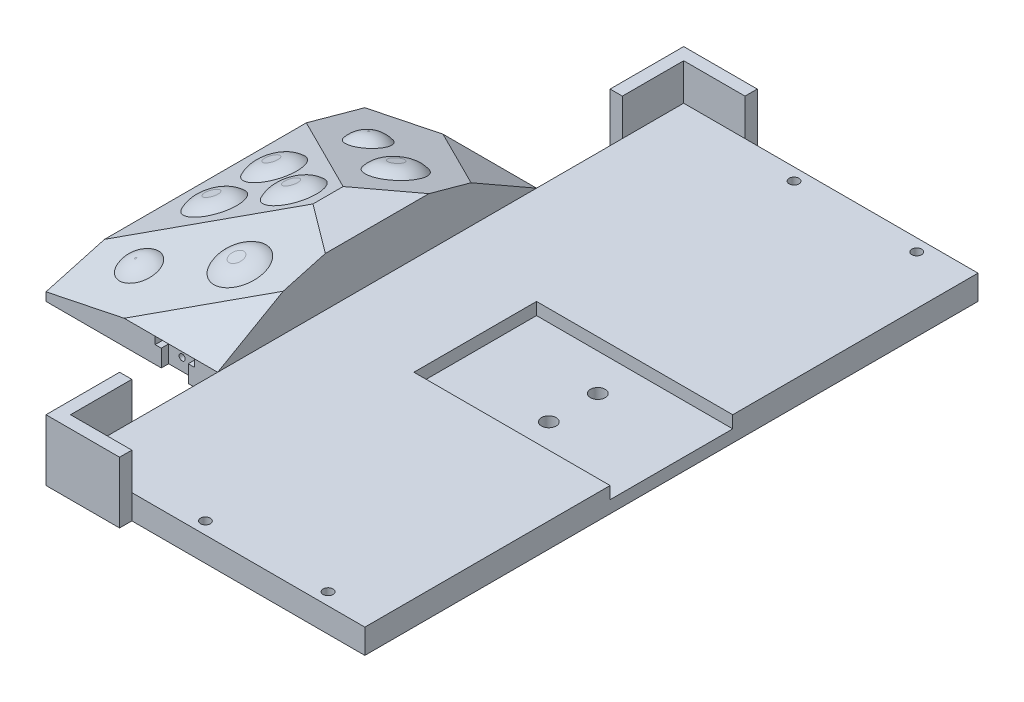
SolidWorks part; units mm, degrees
ref_plane "Ebene vorne" through (0, 0, 0) normal (0, 0, 1) x (1, 0, 0)
ref_plane "Ebene oben" through (0, 0, 0) normal (0, 1, 0) x (1, 0, 0)
ref_plane "Ebene rechts" through (0, 0, 0) normal (1, 0, 0) x (0, 0, -1)
sketch "Skizze1" plane through (0, 0, 0) normal (0, 1, 0) x (1, 0, 0)
  line L5 (-175, -125) -> (175, 125) construction
  line L6 (-175, 125) -> (175, -125) construction
  line L11 (-105, 125) -> (145, 125)
  line L12 (-105, -125) -> (-105, -65)
  line L13 (-105, 125) -> (-105, 65)
  line L14 (-105, -65) -> (-175, -65)
  line L15 (-105, 65) -> (-175, 65)
  line L17 (-105, -125) -> (145, -125)
  line L19 (185, 20) -> (145, 125)
  line L21 (175, 0) -> (175, 20)
  line L22 (175, 20) -> (185, 20)
  line L23 (185, 0) -> (185, 20)
  line L25 (185, 0) -> (185, -20)
  line L26 (185, -20) -> (175, -20)
  line L27 (175, 0) -> (175, -20)
  line L28 (185, -20) -> (145, -125)
  line L29 (-175, 65) -> (-175, -65)
  point P0 (0, 0)
  dimension "D1" = 350
  dimension "D2" = 250
  dimension "D3" = 60
  dimension "D4" = 250
  dimension "D5" = 40
  dimension "D6" = 130
  dimension "D7" = 70
  dimension "D8" = 20
  dimension "D9" = 10
extrude "Aufsatz-Linear austragen1" add sketch "Skizze1" along normal blind 15 contours L15 L29 L14 L12 L17 L28 L26 L27 L21 L22 L19 L11 L13 | L21 L27 L26 L25 L23 L22 region at (10.8182, 0, 0) region at (180, 0, 0)
sketch "Skizze2" plane through (0, 15, 0) normal (0, 1, 0) x (1, 0, 0)
  line L0 (-175, 65) -> (-175, -65) construction
  line L9 (-175, 62) -> (-110, 62)
  line L10 (-175, 62) -> (-175, 42)
  line L11 (-175, 42) -> (-110, 42)
  line L12 (-110, 62) -> (-110, 42)
  line L13 (-105, 65) -> (-175, 65) construction
  line L14 (-175, -42) -> (-110, -42)
  line L15 (-175, -42) -> (-175, -62)
  line L16 (-175, -62) -> (-110, -62)
  line L17 (-110, -42) -> (-110, -62)
  line L18 (-105, -65) -> (-175, -65) construction
  line L19 (-105, 125) -> (145, 125) construction
  line L24 (-125, -62) -> (-120, -62)
  line L25 (-125, -62) -> (-125, -65)
  line L26 (-125, -65) -> (-120, -65)
  line L27 (-120, -62) -> (-120, -65)
  line L28 (-125, -42) -> (-120, -42)
  line L29 (-125, -42) -> (-125, -38)
  line L30 (-125, -38) -> (-120, -38)
  line L31 (-120, -42) -> (-120, -38)
  line L32 (-125, 42) -> (-120, 42)
  line L33 (-125, 42) -> (-125, 38)
  line L34 (-125, 38) -> (-120, 38)
  line L35 (-120, 42) -> (-120, 38)
  line L36 (-125, 65) -> (-120, 65)
  line L37 (-125, 65) -> (-125, 62)
  line L38 (-125, 62) -> (-120, 62)
  line L39 (-120, 65) -> (-120, 62)
  line L40 (-105, -125) -> (145, -125)
  line L41 (-105, -125) -> (-105, 125)
  line L42 (-105, 125) -> (145, 125)
  line L43 (145, -125) -> (145, 125)
  line L46 (145, -125) -> (195, -125)
  line L47 (145, -125) -> (145, 125)
  line L48 (145, 125) -> (195, 125)
  line L49 (195, -125) -> (195, 125)
  line M8 (-105, 65) -> (-175, 65)
  dimension "D1" = 65
  dimension "D2" = 65
  dimension "D3" = 20
  dimension "D4" = 20
  dimension "D5" = 3
  dimension "D6" = 3
  dimension "D7" = 5
  dimension "D8" = 50
  dimension "D9" = 5
  dimension "D10" = 50
  dimension "D11" = 5
  dimension "D12" = 50
  dimension "D13" = 5
  dimension "D14" = 50
  dimension "D15" = 4
  dimension "D16" = 4
  dimension "D17" = 250
  dimension "D18" = 50
extrude "Aufsatz-Linear austragen2" add sketch "Skizze2" against normal blind 37 contours L14 L31 L30 L29 | L35 L11 L33 L34 | L39 L37 L9 M8 | L26 L27 L24 L25 region at (-122.5, 15, -63.5) region at (-122.5, 15, -40) region at (-122.5, 15, 40)
sketch "Skizze3" plane through (0, 15, 0) normal (0, 1, 0) x (1, 0, 0)
  line L0 (-105, 125) -> (145, 125) construction
  line L1 (-105, -125) -> (145, -125)
  line L2 (-105, -125) -> (-105, 125)
  line L3 (-105, 125) -> (145, 125)
  line L4 (145, -125) -> (145, 125)
  line L6 (145, -125) -> (195, -125)
  line L7 (145, -125) -> (145, 125)
  line L8 (145, 125) -> (195, 125)
  line L9 (195, -125) -> (195, 125)
  line M6 (145, -125) -> (185, -20)
  line M7 (185, -20) -> (185, 20)
  line M8 (185, 20) -> (145, 125)
  dimension "D1" = 250
  dimension "D2" = 50
extrude "Aufsatz-Linear austragen3" add sketch "Skizze3" against normal blind 15 contours L6 L9 L8 M8 M7 M6 region at (167.3825, 15, 73.4076)
sketch "Skizze4" plane through (0, 15, 0) normal (0, 1, 0) x (1, 0, 0)
  line L9 (195, -125) -> (200, -125)
  line L10 (195, -125) -> (195, 125)
  line L11 (195, 125) -> (200, 125)
  line L12 (200, -125) -> (200, 125)
  dimension "D3" = 250
  dimension "D4" = 5
extrude "Aufsatz-Linear austragen4" add sketch "Skizze4" against normal blind 15
sketch "Skizze5" plane through (0, 15, 0) normal (0, 1, 0) x (1, 0, 0)
  line L1 (-105, 125) -> (-75, 125)
  line L2 (-105, 125) -> (-105, 120)
  line L3 (-105, 120) -> (-75, 120)
  line L4 (-75, 125) -> (-75, 120)
  line L5 (-105, -125) -> (-75, -125)
  line L6 (-105, -125) -> (-105, -120)
  line L7 (-105, -120) -> (-75, -120)
  line L8 (-75, -125) -> (-75, -120)
  dimension "D1" = 30
  dimension "D2" = 30
  dimension "D3" = 5
  dimension "D4" = 5
extrude "Aufsatz-Linear austragen5" add sketch "Skizze5" against normal blind 30
sketch "Skizze6" plane through (0, 15, 0) normal (0, 1, 0) x (1, 0, 0)
  line L0 (-105, -125) -> (200, -125) construction
  line L1 (-110, -130) -> (-70.4119, -130)
  line L2 (-110, -130) -> (-110, -86.8064)
  line L3 (-110, -86.8064) -> (-70.4119, -86.8064)
  line L4 (-70.4119, -130) -> (-70.4119, -86.8064)
  line L5 (-110, 130) -> (-61.5934, 130)
  line L6 (-110, 130) -> (-110, 88.8696)
  line L7 (-110, 88.8696) -> (-61.5934, 88.8696)
  line L8 (-61.5934, 130) -> (-61.5934, 88.8696)
  line L9 (-105, -125) -> (-105, -65) construction
  line L10 (-105, 125) -> (-105, 65) construction
  line L11 (-105, 125) -> (200, 125) construction
  line L12 (-68.8744, -125) -> (-105, -125)
  line L13 (-105, -125) -> (-105, -86.8064)
  line L14 (-105, 84.0053) -> (-105, 125)
  line L15 (-105, 125) -> (-61.5934, 125)
  line M6 (-105, -65) -> (-105, -125)
  line M7 (-105, -125) -> (200, -125)
  line M9 (200, 125) -> (-105, 125)
  line M10 (-105, 125) -> (-105, 65)
  dimension "D1" = 5
  dimension "D2" = 5
  dimension "D3" = 5
  dimension "D4" = 5
extrude "Aufsatz-Linear austragen6" add sketch "Skizze6" along normal blind 15 separate body contours L8 L5 L6 L7 M10 M9 | L1 L4 L3 L2 M7 M6 region at (-109.4141, 15, 108.4032) region at (-85.7967, 15, -129.3648)
sketch "Skizze7" plane through (0, 0, 0) normal (0, -1, 0) x (1, 0, 0)
  line L7 (-110, -130) -> (-110, -88.8696)
  line L8 (-110, -88.8696) -> (-105, -88.8696)
  line L9 (-105, -130) -> (-105, -88.8696)
  line L10 (-110, 130) -> (-105, 130)
  line L11 (-110, 130) -> (-110, 86.8064)
  line L12 (-110, 86.8064) -> (-105, 86.8064)
  line L13 (-105, 130) -> (-105, 86.8064)
  line L14 (-110, 130) -> (-70.4119, 130)
  line L15 (-110, 130) -> (-110, 125)
  line L16 (-110, 125) -> (-70.4119, 125)
  line L17 (-70.4119, 130) -> (-70.4119, 125)
  line L18 (-110, -130) -> (-61.5934, -130)
  line L19 (-110, -130) -> (-110, -125)
  line L20 (-110, -125) -> (-61.5934, -125)
  line L21 (-61.5934, -130) -> (-61.5934, -125)
  line M7 (-105, 120) -> (-105, 65)
  line M19 (-105, -65) -> (-105, -120)
  line M22 (-75, -125) -> (200, -125)
  line M24 (200, 125) -> (-75, 125)
extrude "Aufsatz-Linear austragen7" add sketch "Skizze7" against normal blind 15 contours L7 L20 L9 L8 M19 | L20 L7 L18 L9 | L18 L21 L20 L9 M22 | L16 L11 L12 L13 M7 | L11 L16 L13 L10 | L17 L14 L13 L16 M24 region at (-107.5, 0, -127.5) region at (-107.5, 0, -106.9348) region at (-83.2967, 0, -127.5) region at (-107.5, 0, 127.5) region at (-87.7059, 0, 127.5) region at (-107.5, 0, 105.9032)
sketch "Skizze8" plane through (0, 15, 0) normal (0, 1, 0) x (1, 0, 0)
  line L0 (-61.5934, 125) -> (200, 125) construction
  line L1 (-105, -125) -> (145, -125)
  line L2 (-105, -125) -> (-105, 125)
  line L3 (-105, 125) -> (145, 125)
  line L4 (145, -125) -> (145, 125)
  line L6 (150, -130) -> (109.2888, -130)
  line L7 (150, -130) -> (150, -94.2536)
  line L8 (150, -94.2536) -> (109.2888, -94.2536)
  line L9 (109.2888, -130) -> (109.2888, -94.2536)
  line L10 (150, 130) -> (118.9946, 130)
  line L11 (150, 130) -> (150, 95.9912)
  line L12 (150, 95.9912) -> (118.9946, 95.9912)
  line L13 (118.9946, 130) -> (118.9946, 95.9912)
  line M9 (-70.4119, -125) -> (200, -125)
  line M11 (200, 125) -> (-61.5934, 125)
  dimension "D1" = 250
  dimension "D2" = 5
  dimension "D3" = 5
  dimension "D4" = 5
  dimension "D5" = 5
extrude "Aufsatz-Linear austragen8" add sketch "Skizze8" along normal blind 15 and the other way blind 15 contours L7 L8 L4 M9 | L9 L6 L7 L1 M9 | L12 L11 L4 M11 | L10 L13 L11 M11 region at (129.6444, 15, 127.5) region at (147.5, 15, 109.6268) region at (134.4973, 15, -127.5) region at (147.5, 15, -110.4956)
sketch "Skizze9" plane through (0, 15, 0) normal (0, 1, 0) x (1, 0, 0)
  line L1 (150, -125) -> (200, -125)
  line L2 (150, -125) -> (150, 125)
  line L3 (150, 125) -> (200, 125)
  line L4 (200, -125) -> (200, 125)
  line L5 (150, 9) -> (196, 9)
  line L6 (150, 9) -> (150, 120)
  line L7 (150, 120) -> (196, 120)
  line L8 (196, 9) -> (196, 120)
  line L10 (200, 105) -> (196, 105)
  line L12 (155, 4) -> (145, 4)
  line L13 (155, 4) -> (155, 14)
  line L14 (155, 14) -> (145, 14)
  line L15 (145, 4) -> (145, 14)
  line L17 (190, 14) -> (200, 14)
  line L18 (190, 14) -> (190, 4)
  line L19 (190, 4) -> (200, 4)
  line L20 (200, 14) -> (200, 4)
  line M10 (150, 125) -> (150, 95.9912)
  line M31 (200, 125) -> (150, 125)
  dimension "D1" = 46
  dimension "D2" = 111
  dimension "D3" = 5
  dimension "D4" = 20
  dimension "D5" = 10
  dimension "D6" = 10
  dimension "D7" = 5
  dimension "D8" = 5
  dimension "D9" = 10
  dimension "D10" = 10
  dimension "D11" = 5
extrude "Aufsatz-Linear austragen10" add sketch "Skizze9" along normal blind 15 contours L15 L12 L2 L14 | L12 L13 L5 L2 | L18 L19 L4 L17 L8 L5 | L10 L4 L7 L8 M31 M10 region at (147.5, 15, -9) region at (152.5, 15, -6.5) region at (195.8571, 15, -7.9286) region at (179.4516, 15, -120.5645)
sketch "Skizze10" plane through (118.9946, 0, 0) normal (-1, 0, 0) x (0, 0, 1)
  line L1 (-125, 30) -> (-130, 30)
  line L2 (-125, 30) -> (-125, 0)
  line L3 (-125, 0) -> (-130, 0)
  line L4 (-130, 30) -> (-130, 0)
extrude "Schnitt-Linear austragen1" cut sketch "Skizze10" against normal blind 1.01
sketch "Skizze12" plane through (0, 15, 0) normal (0, 1, 0) x (1, 0, 0)
  line L0 (-105, 125) -> (-105, 88.8696) construction
  line L1 (-110, 130) -> (-105, 130)
  line L2 (-110, 130) -> (-110, 100)
  line L3 (-110, 100) -> (-105, 100)
  line L4 (-105, 130) -> (-105, 100)
  line L5 (145, 95.9912) -> (145, 125) construction
  line L6 (-105, -125) -> (-70.4119, -125) construction
  line L7 (-110, -130) -> (-80, -130)
  line L8 (-110, -130) -> (-110, -125)
  line L9 (-110, -125) -> (-80, -125)
  line L10 (-80, -130) -> (-80, -125)
  line L11 (-61.5934, 125) -> (-105, 125) construction
  line L12 (-110, 130) -> (-80, 130)
  line L13 (-110, 130) -> (-110, 125)
  line L14 (-110, 125) -> (-80, 125)
  line L15 (-80, 130) -> (-80, 125)
  line L16 (120.0046, 125) -> (145, 125) construction
  line L17 (150, 130) -> (120, 130)
  line L18 (150, 130) -> (150, 125)
  line L19 (150, 125) -> (120, 125)
  line L20 (120, 130) -> (120, 125)
  line L21 (150, 130) -> (145, 130)
  line L22 (150, 130) -> (150, 100)
  line L23 (150, 100) -> (145, 100)
  line L24 (145, 130) -> (145, 100)
  line L25 (145, -125) -> (145, -94.2536) construction
  line L26 (150, -130) -> (145, -130)
  line L27 (150, -130) -> (150, -100)
  line L28 (150, -100) -> (145, -100)
  line L29 (145, -130) -> (145, -100)
  line L30 (109.2888, -125) -> (145, -125) construction
  line L31 (150, -130) -> (120, -130)
  line L32 (150, -130) -> (150, -125)
  line L33 (150, -125) -> (120, -125)
  line L34 (120, -130) -> (120, -125)
  line L36 (-105, -86.8064) -> (-105, -125) construction
  line L37 (-110, -130) -> (-105, -130)
  line L38 (-110, -130) -> (-110, -100)
  line L39 (-110, -100) -> (-105, -100)
  line L40 (-105, -130) -> (-105, -100)
  line L42 (-80, -125) -> (-70.4119, -125)
  line L43 (-80, -125) -> (-80, -130)
  line L44 (-80, -130) -> (-70.4119, -130)
  line L45 (-70.4119, -125) -> (-70.4119, -130)
  line L46 (-105, -100) -> (-110, -100)
  line L47 (-105, -100) -> (-105, -86.8064)
  line L48 (-105, -86.8064) -> (-110, -86.8064)
  line L49 (-110, -100) -> (-110, -86.8064)
  line L50 (-105, 100) -> (-110, 100)
  line L51 (-105, 100) -> (-105, 88.8696)
  line L52 (-105, 88.8696) -> (-110, 88.8696)
  line L53 (-110, 100) -> (-110, 88.8696)
  line L54 (-80, 125) -> (-61.5934, 125)
  line L55 (-80, 125) -> (-80, 130)
  line L56 (-80, 130) -> (-61.5934, 130)
  line L57 (-61.5934, 125) -> (-61.5934, 130)
  line L58 (150, 100) -> (145, 100)
  line L59 (150, 100) -> (150, 95.9912)
  line L60 (150, 95.9912) -> (145, 95.9912)
  line L61 (145, 100) -> (145, 95.9912)
  line L62 (150, -100) -> (145, -100)
  line L63 (150, -100) -> (150, -94.2536)
  line L64 (150, -94.2536) -> (145, -94.2536)
  line L65 (145, -100) -> (145, -94.2536)
  line L66 (120, -125) -> (109.2888, -125)
  line L67 (120, -125) -> (120, -130)
  line L68 (120, -130) -> (109.2888, -130)
  line L69 (109.2888, -125) -> (109.2888, -130)
  line M12 (150, 120) -> (150, 95.9912)
  line M13 (150, 95.9912) -> (145, 95.9912)
  line M14 (145, 95.9912) -> (145, 125)
  line M17 (-61.5934, 125) -> (-105, 125)
  line M18 (-105, 125) -> (-105, 88.8696)
  line M24 (-105, -86.8064) -> (-105, -125)
  line M25 (-105, -125) -> (-70.4119, -125)
  line M27 (109.2888, -125) -> (145, -125)
  line M28 (145, -125) -> (145, -94.2536)
  line M29 (145, -94.2536) -> (150, -94.2536)
  line M30 (150, -94.2536) -> (150, -125)
  dimension "D1" = 30
  dimension "D2" = 30
  dimension "D3" = 30
  dimension "D4" = 30
  dimension "D5" = 30
  dimension "D6" = 30
  dimension "D7" = 30
  dimension "D8" = 30
extrude "Schnitt-Linear austragen2" cut sketch "Skizze12" along normal blind 15 contours L69 L68 L34 M27 | L28 M30 M29 M28 | L23 M12 M14 M13 | L57 L56 L15 M17 | L3 L53 L52 M18 | L45 L10 L44 M25 | L49 L39 L48 M24 region at (-70.7967, 15, -127.5) region at (-107.5, 15, -94.4348) region at (-75.2059, 15, 127.5) region at (-107.5, 15, 93.4032) region at (147.5, 15, -97.9956) region at (114.6444, 15, 127.5) region at (147.5, 15, 97.1268)
sketch "Skizze13" plane through (0, 15, 0) normal (0, 1, 0) x (1, 0, 0)
  line L1 (109.2888, -130) -> (120, -130)
  line L2 (109.2888, -130) -> (109.2888, -125)
  line L3 (109.2888, -125) -> (120, -125)
  line L4 (120, -130) -> (120, -125)
  line L5 (-70.4119, -130) -> (-80, -130)
  line L6 (-70.4119, -130) -> (-70.4119, -125)
  line L7 (-70.4119, -125) -> (-80, -125)
  line L8 (-80, -130) -> (-80, -125)
  line L9 (-110, -86.8064) -> (-105, -86.8064)
  line L10 (-110, -86.8064) -> (-110, -100)
  line L11 (-110, -100) -> (-105, -100)
  line L12 (-105, -86.8064) -> (-105, -100)
  line L13 (-110, 88.8696) -> (-105, 88.8696)
  line L14 (-110, 88.8696) -> (-110, 100)
  line L15 (-110, 100) -> (-105, 100)
  line L16 (-105, 88.8696) -> (-105, 100)
  line L17 (-61.5934, 130) -> (-80, 130)
  line L18 (-61.5934, 130) -> (-61.5934, 125)
  line L19 (-61.5934, 125) -> (-80, 125)
  line L20 (-80, 130) -> (-80, 125)
extrude "Schnitt-Linear austragen3" cut sketch "Skizze13" against normal blind 15
sketch "Skizze14" plane through (0, 15, 0) normal (0, 1, 0) x (1, 0, 0)
  line L1 (-175, -65) -> (-105, -65)
  line L2 (-175, -65) -> (-175, 65)
  line L3 (-175, 65) -> (-105, 65)
  line L4 (-105, -65) -> (-105, 65)
  line L5 (-175, -25) -> (-105, -25)
  line L6 (-175, -25) -> (-175, 25)
  line L7 (-175, 25) -> (-105, 25)
  line L8 (-105, -25) -> (-105, 25)
  line L9 (-105, -25) -> (-125, -25)
  line L10 (-105, -25) -> (-105, 25)
  line L11 (-105, 25) -> (-125, 25)
  line L12 (-125, -25) -> (-125, 25)
  line M34 (-105, 65) -> (-175, 65)
  line M35 (-175, 65) -> (-175, -65)
  line M36 (-175, -65) -> (-105, -65)
  dimension "D1" = 50
  dimension "D2" = 40
  dimension "D3" = 20
  dimension "D4" = 50
extrude "Aufsatz-Linear austragen11" add sketch "Skizze14" along normal blind 20 contours L5 L2 L4 M36 | L5 L12 L7 L2 | L12 L5 L4 L7 | L7 L4 M35 M34 region at (-140, 15, 45) region at (-150, 15, 0) region at (-115, 15, 0) region at (-140, 15, -45)
chamfer "Fase2" distance 20 distance2 50 1 edges at (-175, 35, 0) first distance on face at (-175, 17.5, 0)
chamfer "Fase3" distance 20 distance2 35 2 edges at (-115, 35, -65) (-115, 35, 65) first distance on face at (-128, 5.6, -65) first distance on face at (-128, 5.6, 65)
chamfer "Fase4" distance 20 distance2 20 2 edges at (-150, 25, 47.5) (-150, 25, -47.5)
sketch "Skizze15" plane through (-11.552, 55.8863, -15.4322) normal (-0.1954, 0.9453, -0.261) x (0.9807, 0.1884, -0.052)
  line L0 (-95.2849, 28.8709) -> (-95.2849, 11.0403) construction
  line L1 (-115.678, -3.3909) -> (-166.6609, 35.67) construction
  circle A0 centre (-117.2849, 20.601) radius 10
  circle A1 centre (-142.8398, 36.3157) radius 7.5
  dimension "D1" = 20
  dimension "D2" = 15
  dimension "D3" = 30
  dimension "D4" = 22
  dimension "D5" = 15
extrude "Aufsatz-Linear austragen12" add sketch "Skizze15" along normal blind 3
fillet "Verrundung1" radius 10 2 edges at (-152.2243, 24.1474, -36.5621) (-127.1621, 33.8091, -20.3337)
sketch "Skizze18" plane through (-11.552, 55.8863, 15.4322) normal (-0.1954, 0.9453, 0.261) x (0.9807, 0.1884, 0.052)
  line L0 (-166.6609, -35.67) -> (-115.678, 3.3909) construction
  line L1 (-95.2849, -11.0403) -> (-95.2849, -28.8709) construction
  circle A0 centre (-117.2849, -25.9789) radius 10
  circle A1 centre (-147.2849, -39.7214) radius 7.5
  dimension "D1" = 20
  dimension "D2" = 15
  dimension "D3" = 30
  dimension "D4" = 15
  dimension "D5" = 22
extrude "Aufsatz-Linear austragen13" add sketch "Skizze18" along normal blind 3
fillet "Verrundung2" radius 10 2 edges at (-156.5838, 18.411, 54.0726) (-127.1621, 27.0541, 44.7961)
sketch "Skizze19" plane through (-29.3103, 73.2759, 0) normal (-0.3714, 0.9285, 0) x (0.9285, 0.3714, 0)
  line L0 (-156.9126, -41.147) -> (-156.9126, 41.147) construction
  line L1 (-103.0609, 6.147) -> (-103.0609, -6.147) construction
  line L3 (-156.9126, -41.147) -> (-103.0609, -6.147) construction
  line L4 (-103.0609, 6.147) -> (-156.9126, 41.147) construction
  circle A0 centre (-118.0609, -0.0632) radius 10
  circle A1 centre (-139.8608, 12.1747) radius 10
  circle A2 centre (-139.9126, -12.2084) radius 10
  dimension "D1" = 15
  dimension "D2" = 15
  dimension "D3" = 17
  dimension "D4" = 17.0518
  dimension "D5" = 25
  dimension "D7" = 15
  dimension "D8" = 25
extrude "Aufsatz-Linear austragen14" add sketch "Skizze19" along normal blind 3
fillet "Verrundung3" radius 10 3 edges at (-149.3261, 28.5007, 0.0632) (-169.6148, 20.3852, 12.2084) (-169.5667, 20.4044, -12.1747)
sketch "Skizze20" plane through (0, 0, -65) normal (0, 0, -1) x (-1, 0, 0)
  line L1 (120, -22) -> (125, -22) construction
  line L2 (120, 0) -> (125, 0)
  line L3 (120, -22) -> (120, 0) construction
  line L4 (125, -22) -> (125, 0) construction
  circle A0 centre (122.5, -19.5) radius 1.5
  circle A1 centre (122.5, -2.5) radius 1.5
  dimension "D1" = 3
  dimension "D2" = 3
  dimension "D3" = 2.5
  dimension "D4" = 2.5
  dimension "D5" = 2.5
  dimension "D6" = 2.5
extrude "Schnitt-Linear austragen4" cut sketch "Skizze20" against normal blind 250 contours A0 | A1 region at (-122.5, -19.5, -65) region at (-122.5, -2.5, -65)
sketch "Skizze21" plane through (0, 15, 0) normal (0, 1, 0) x (1, 0, 0)
  line L0 (200, -125) -> (200, 4) construction
  line L1 (197.5893, -53.9558) -> (147.5893, -53.9558)
  line L2 (197.5893, -53.9558) -> (197.5893, 1.0442)
  line L3 (197.5893, 1.0442) -> (147.5893, 1.0442)
  line L4 (147.5893, -53.9558) -> (147.5893, 1.0442)
  line L9 (150, -100) -> (191, -100)
  line L10 (150, -100) -> (150, -118)
  line L11 (150, -118) -> (191, -118)
  line L12 (191, -100) -> (191, -118)
  line L13 (145, -100) -> (195, -100)
  line L14 (145, -100) -> (145, -93)
  line L15 (145, -93) -> (195, -93)
  line L16 (195, -100) -> (195, -93)
  line L17 (150, -125) -> (200, -125)
  line L18 (150, -125) -> (150, -118)
  line L19 (150, -118) -> (200, -118)
  line L20 (200, -125) -> (200, -118)
  line L22 (195, -93) -> (191, -93)
  line L23 (195, -93) -> (195, -105.2)
  line L24 (195, -105.2) -> (191, -105.2)
  line L25 (191, -93) -> (191, -105.2)
  line L26 (195, -125) -> (191, -125)
  line L27 (195, -125) -> (195, -112.8)
  line L28 (195, -112.8) -> (191, -112.8)
  line L29 (191, -125) -> (191, -112.8)
  line M31 (145, -100) -> (150, -100)
  line M32 (150, -100) -> (150, -125)
  line M33 (150, -125) -> (200, -125)
  dimension "D1" = 55
  dimension "D2" = 50
  dimension "D3" = 41
  dimension "D4" = 18
  dimension "D5" = 7
  dimension "D6" = 4
  dimension "D7" = 12.2
  dimension "D8" = 4
  dimension "D9" = 12.2
extrude "Aufsatz-Linear austragen15" add sketch "Skizze21" along normal blind 10 contours L25 L15 L14 L9 M31 | L15 L25 L13 L16 | L24 L23 L13 L12 | L29 L11 M33 M32 | L29 L17 L27 L19 | L27 L28 L12 L19 region at (168, 15, 96.5) region at (193, 15, 102.6) region at (193, 15, 96.5) region at (170.5, 15, 121.5) region at (193, 15, 115.4) region at (193, 15, 121.5)
sketch "Skizze22" plane through (0, 15, 0) normal (0, 1, 0) x (1, 0, 0)
  line L1 (140.9695, -63.333) -> (190.9695, -63.333)
  line L2 (140.9695, -63.333) -> (140.9695, -8.333)
  line L3 (140.9695, -8.333) -> (190.9695, -8.333)
  line L4 (190.9695, -63.333) -> (190.9695, -8.333)
  circle A0 centre (146.0695, -58.233) radius 1.75
  circle A1 centre (146.0695, -13.433) radius 1.75
  circle A2 centre (185.8695, -58.233) radius 1.75
  circle A3 centre (185.8695, -13.433) radius 1.75
  dimension "D1" = 3.5
  dimension "D2" = 3.5
  dimension "D3" = 3.5
  dimension "D4" = 3.5
  dimension "D5" = 5.1
  dimension "D6" = 5.1
  dimension "D7" = 50
  dimension "D8" = 55
  dimension "D9" = 5.1
  dimension "D10" = 5.1
  dimension "D11" = 5.1
  dimension "D12" = 5.1
  dimension "D13" = 5.1
  dimension "D14" = 5.1
extrude "Schnitt-Linear austragen5" cut sketch "Skizze22" against normal blind 20 contours A0 | A1 | A3 | A2
sketch "Skizze25" plane through (0, 15, 0) normal (0, 1, 0) x (1, 0, 0)
  line L0 (-175, -41.147) -> (-175, 41.147) construction
  line L1 (15, 146.8783) -> (227.9673, 146.8783)
  line L2 (15, 146.8783) -> (15, -156.3563)
  line L3 (15, -156.3563) -> (227.9673, -156.3563)
  line L4 (227.9673, 146.8783) -> (227.9673, -156.3563)
  dimension "D1" = 190
extrude "Schnitt-Linear austragen8" cut sketch "Skizze25" against normal blind 50 and the other way blind 50
sketch "Skizze26" plane through (15, 0, 0) normal (1, 0, 0) x (0, 0, -1)
  line L0 (-125, 15) -> (125, 15) construction
  line L1 (-25, 15) -> (25, 15)
  line L2 (-25, 15) -> (-25, 10)
  line L3 (-25, 10) -> (25, 10)
  line L4 (25, 15) -> (25, 10)
  line L7 (125, 15) -> (125, 0) construction
  dimension "D1" = 5
  dimension "D2" = 50
  dimension "D3" = 100
extrude "Schnitt-Linear austragen9" cut sketch "Skizze26" against normal blind 80
sketch "Skizze27" plane through (0, 15, 0) normal (0, 1, 0) x (1, 0, 0)
  line L1 (15, -25) -> (-65, -25)
  line L2 (15, -25) -> (15, 25)
  line L3 (15, 25) -> (-65, 25)
  line L4 (-65, -25) -> (-65, 25)
sketch "Skizze28" plane through (0, 10, 0) normal (0, 1, 0) x (1, 0, 0)
  line L0 (-65, 25) -> (15, 25) construction
  line L1 (-65, -25) -> (-65, 25) construction
  circle A0 centre (-35, 0) radius 12.5
  dimension "D3" = 25
  dimension "D1" = 25
  dimension "D2" = 30
extrude "Schnitt-Linear austragen10" cut sketch "Skizze28" against normal blind 80
sketch "Skizze29" plane through (0, 0, 0) normal (0, -1, 0) x (-1, 0, 0)
  circle A0 centre (35, 0) radius 23.1296
extrude "Aufsatz-Linear austragen16" add sketch "Skizze29" against normal blind 10
sketch "Skizze32" plane through (0, 15, 0) normal (0, 1, 0) x (1, 0, 0)
  line L0 (15, 125) -> (-105, 125)
  line L16 (15, -25) -> (-65, -25)
  line L17 (-65, -25) -> (-65, 25)
  line L18 (-65, 25) -> (15, 25)
  line L19 (15, 25) -> (15, 125)
  line L20 (15, 125) -> (-80, 125)
  line L21 (-80, 125) -> (-105, 125)
  line L22 (-105, 125) -> (-105, 100)
  line L23 (-105, 100) -> (-105, 65)
  line L24 (-105, 65) -> (-105, -65)
  line L25 (-105, -65) -> (-105, -100)
  line L26 (-105, -100) -> (-105, -125)
  line L27 (-105, -125) -> (-80, -125)
  line L28 (-80, -125) -> (15, -125)
  line L29 (15, -125) -> (15, -25)
  line L34 (15, 125) -> (-80, 125)
  line L35 (-80, 125) -> (-105, 125)
  dimension "D1" = 0
sketch "Skizze33" plane through (-65, 0, 0) normal (1, 0, 0) x (0, 0, -1)
  line L1 (-25, 15) -> (25, 15)
  line L2 (-25, 15) -> (-25, 10)
  line L3 (-25, 10) -> (25, 10)
  line L4 (25, 15) -> (25, 10)
extrude "Aufsatz-Linear austragen17" add sketch "Skizze33" along normal blind 160
sketch "Skizze34" plane through (0, 0, 0) normal (0, -1, 0) x (-1, 0, 0)
  line L1 (65, 25) -> (-95, 25)
  line L2 (65, 25) -> (65, -25)
  line L3 (65, -25) -> (-95, -25)
  line L4 (-95, 25) -> (-95, -25)
extrude "Aufsatz-Linear austragen18" add sketch "Skizze34" along normal blind 15
sketch "Skizze36" plane through (0, 0, 125) normal (0, 0, 1) x (1, 0, 0)
  line L1 (-105, -15) -> (-75, -15) construction
  line L2 (-75, -15) -> (-75, 0) construction
  circle A0 centre (-97.5, -7.5) radius 2.5
  circle A1 centre (-82.5, -7.5) radius 2.5
  dimension "D5" = 5
  dimension "D6" = 5
  dimension "D1" = 7.5
  dimension "D2" = 7.5
  dimension "D3" = 15
  dimension "D4" = 7.5
extrude "Schnitt-Linear austragen12" cut sketch "Skizze36" against normal blind 250
sketch "Skizze37" plane through (0, 15, 0) normal (0, 1, 0) x (1, 0, 0)
  line L1 (15, -25) -> (95, -25)
  line L2 (15, -25) -> (15, 25)
  line L3 (15, 25) -> (95, 25)
  line L4 (95, -25) -> (95, 25)
  circle A0 centre (35, -10) radius 3
  circle A1 centre (35, 10) radius 3
  circle A2 centre (75, -10) radius 3
  circle A3 centre (75, 10) radius 3
  dimension "D1" = 6
  dimension "D2" = 6
  dimension "D3" = 6
  dimension "D4" = 6
  dimension "D7" = 15
  dimension "D5" = 20
  dimension "D6" = 15
  dimension "D8" = 20
  dimension "D9" = 20
  dimension "D10" = 20
  dimension "D11" = 40
  dimension "D12" = 40
extrude "Schnitt-Linear austragen16" cut sketch "Skizze37" against normal blind 78 contours A0 | A1 | A2 | A3
sketch "Skizze38" plane through (0, 15, 0) normal (0, 1, 0) x (1, 0, 0)
  line L0 (15, -125) -> (15, -25) construction
  line L1 (15, 25) -> (15, 125) construction
  line L2 (15, 125) -> (-105, 125) construction
  line L3 (-80, -125) -> (15, -125) construction
  circle A0 centre (-55, -120) radius 2
  circle A1 centre (-5, -120) radius 2
  circle A2 centre (-5, 120) radius 2
  circle A3 centre (-55, 120) radius 2
  dimension "D1" = 4
  dimension "D2" = 4
  dimension "D3" = 4
  dimension "D4" = 4
  dimension "D11" = 5
  dimension "D5" = 20
  dimension "D6" = 50
  dimension "D7" = 20
  dimension "D8" = 50
  dimension "D9" = 5
  dimension "D10" = 5
  dimension "D12" = 5
extrude "Schnitt-Linear austragen17" cut sketch "Skizze38" against normal blind 50 contours A1 | A0 | A3 | A2
sketch "Skizze39" plane through (0, -15, 0) normal (0, -1, 0) x (-1, 0, 0)
  line L1 (-95, -25) -> (65, -25)
  line L2 (-95, -25) -> (-95, 25)
  line L3 (-95, 25) -> (65, 25)
  line L4 (65, -25) -> (65, 25)
  dimension "D1" = 160
  dimension "D2" = 50
extrude "Schnitt-Linear austragen18" cut sketch "Skizze39" against normal blind 15
sketch "Skizze40" plane through (0, 10, 0) normal (0, -1, 0) x (1, 0, 0)
  line L0 (95, 25) -> (95, -25) construction
  line L1 (95, -25) -> (15, -25) construction
  line L3 (-65, 25) -> (95, 25)
  line L4 (-65, 25) -> (-65, -25)
  line L5 (-65, -25) -> (95, -25)
  line L6 (95, 25) -> (95, -25)
  circle A0 centre (35, -10) radius 3
  circle A1 centre (75, -10) radius 3
  dimension "D4" = 6
  dimension "D1" = 40
  dimension "D2" = 20
  dimension "D3" = 15
extrude "Schnitt-Linear austragen19" cut sketch "Skizze40" against normal blind 5
sketch "Skizze41" plane through (0, 10, 0) normal (0, 1, 0) x (1, 0, 0)
  line L0 (15, -25) -> (-65, -25) construction
  line L1 (-65, -25) -> (-65, 25) construction
  circle A0 centre (-25, -10) radius 3
  circle A1 centre (-25, 10) radius 3
  dimension "D4" = 6
  dimension "D5" = 6
  dimension "D1" = 20
  dimension "D2" = 15
  dimension "D3" = 40
extrude "Schnitt-Linear austragen22" cut sketch "Skizze41" against normal blind 10
sketch "Skizze46" plane through (0, 0, 130) normal (0, 0, 1) x (1, 0, 0)
  line L0 (15, 15) -> (15, 0) construction
  line L1 (-175, 0) -> (15, 0)
  line L2 (-175, 0) -> (-175, 5)
  line L3 (-175, 5) -> (15, 5)
  line L4 (15, 0) -> (15, 5)
  line L6 (-175, 5) -> (16.7135, 5)
  line L7 (-175, 5) -> (-175, -27.4052)
  line L8 (-175, -27.4052) -> (16.7135, -27.4052)
  line L9 (16.7135, 5) -> (16.7135, -27.4052)
  line M2 (-110, 0) -> (-80, 0)
  line M3 (-80, 0) -> (-80, 30)
  line M5 (-110, 30) -> (-110, 0)
  dimension "D1" = 5
extrude "Schnitt-Linear austragen25" cut sketch "Skizze46" against normal blind 268 contours L3 L2 L1 M5 | L9 L6 L4 L1 L7 L8 M2 | L3 M5 M2 M3 | L1 L4 L3 M3 region at (-142.5, 2.5, 130) region at (-78.9886, -13.6762, 130) region at (-95, 2.5, 130) region at (-32.5, 2.5, 130)
sketch "Skizze48" plane through (0, 0, 65) normal (0, 0, 1) x (1, 0, 0)
  line L0 (-175, 5) -> (-105, 5) construction
  line L1 (-126, 5) -> (-119, 5)
  line L2 (-126, 5) -> (-126, 15)
  line L3 (-126, 15) -> (-119, 15)
  line L4 (-119, 5) -> (-119, 15)
  line L5 (-175, 8.4133) -> (-175, 5) construction
  dimension "D1" = 49
  dimension "D2" = 7
  dimension "D3" = 10
extrude "Schnitt-Linear austragen26" cut sketch "Skizze48" against normal blind 33
sketch "Skizze49" plane through (0, 0, -65) normal (0, 0, -1) x (-1, 0, 0)
  line L0 (175, 5) -> (105, 5) construction
  line L1 (119, 5) -> (126, 5)
  line L2 (119, 5) -> (119, 15)
  line L3 (119, 15) -> (126, 15)
  line L4 (126, 5) -> (126, 15)
  line L5 (143.1349, 15) -> (105, 15) construction
  line L6 (175, 8.4133) -> (175, 5) construction
  dimension "D1" = 49
  dimension "D2" = 7
extrude "Schnitt-Linear austragen28" cut sketch "Skizze49" against normal blind 33
sketch "Skizze50" plane through (0, 15, 0) normal (0, -1, 0) x (1, 0, 0)
  line L0 (-126, -32) -> (-119, -32) construction
  line L1 (-119, 32) -> (-126, 32) construction
  line L2 (-119, -32) -> (-119, -65) construction
  line L3 (-119, 32) -> (-119, 65) construction
  circle A0 centre (-122.5, -44) radius 1.65
  circle A1 centre (-122.5, 44) radius 1.65
  point P6 (-122.5, -32)
  dimension "D1" = 3.3
  dimension "D3" = 3.3
  dimension "D2" = 12
  dimension "D4" = 12
  dimension "D5" = 3.5
  dimension "D6" = 3.5
extrude "Schnitt-Linear austragen31" cut sketch "Skizze50" against normal blind 7
sketch "Skizze52" plane through (0, 5, 0) normal (0, -1, 0) x (1, 0, 0)
  circle A0 centre (-123.1916, -39.6891) radius 7.4051
  circle A1 centre (-121.4416, 38.4522) radius 8.306
extrude "Aufsatz-Linear austragen31" add sketch "Skizze52" against normal blind 17
sketch "Skizze53" plane through (0, 5, 0) normal (0, -1, 0) x (1, 0, 0)
  line L0 (-175, -65) -> (-126, -65) construction
  line L1 (-130.9001, -62) -> (-110.0599, -62)
  line L2 (-130.9001, -62) -> (-130.9001, 62)
  line L3 (-130.9001, 62) -> (-110.0599, 62)
  line L4 (-110.0599, -62) -> (-110.0599, 62)
  line L5 (-175, 65) -> (-126, 65) construction
  dimension "D1" = 3
  dimension "D2" = 3
extrude "Aufsatz-Linear austragen34" add sketch "Skizze53" against normal blind 10
sketch "Skizze54" plane through (0, 0, -65) normal (0, 0, -1) x (-1, 0, 0)
  line L0 (119, 15) -> (105, 15) construction
  line L1 (116.5, 15) -> (128.5, 15)
  line L2 (116.5, 15) -> (116.5, 12)
  line L3 (116.5, 12) -> (128.5, 12)
  line L4 (128.5, 15) -> (128.5, 12)
  line L6 (126, 15) -> (126, 5)
  line M4 (143.1349, 15) -> (126, 15)
  line M5 (126, 15) -> (126, 5)
  dimension "D1" = 12
  dimension "D2" = 2.5
  dimension "D3" = 3
extrude "Schnitt-Linear austragen32" cut sketch "Skizze54" against normal blind 3 contours L2 L3 L1 M5 | L4 L3 M4 M5 region at (-121.25, 13.5, -65) region at (-127.25, 13.5, -65)
sketch "Skizze55" plane through (0, 0, 62) normal (0, 0, 1) x (1, 0, 0)
  line L0 (-105, 15) -> (-119, 15) construction
  line L1 (-116.5, 15) -> (-128.5, 15)
  line L2 (-116.5, 15) -> (-116.5, 12)
  line L3 (-116.5, 12) -> (-128.5, 12)
  line L4 (-128.5, 15) -> (-128.5, 12)
  line L5 (-126, 15) -> (-126, 5)
  line M4 (-126, 15) -> (-126, 5)
  line M6 (-119, 5) -> (-119, 15)
  dimension "D1" = 12
  dimension "D2" = 2.5
  dimension "D3" = 3
extrude "Schnitt-Linear austragen34" cut sketch "Skizze55" along normal blind 6 contours L1 L4 L3 M4 | L3 L2 L1 M6 region at (-117.75, 13.5, 62) region at (-127.25, 13.5, 62)
sketch "Skizze57" plane through (0, 0, -62) normal (0, 0, -1) x (-1, 0, 0)
  line L0 (128.5, 15) -> (116.5, 15) construction
  line L1 (119, 5) -> (119, 12) construction
  circle A0 centre (122.5, 10) radius 1.25
  dimension "D1" = 2.5
  dimension "D2" = 5
  dimension "D3" = 3.5
extrude "Schnitt-Linear austragen35" cut sketch "Skizze57" against normal blind 131
sketch "Skizze58" plane through (0, 5, 0) normal (0, -1, 0) x (-1, 0, 0)
  line L0 (119, 65) -> (105, 65) construction
  line L1 (108.2584, 55) -> (138.7587, 55)
  line L2 (108.2584, 55) -> (108.2584, -55)
  line L3 (108.2584, -55) -> (138.7587, -55)
  line L4 (138.7587, 55) -> (138.7587, -55)
  line L5 (119, -65) -> (105, -65) construction
  dimension "D1" = 10
  dimension "D2" = 10
extrude "Aufsatz-Linear austragen35" add sketch "Skizze58" against normal blind 10
sketch "Skizze59" plane through (0, 5, 0) normal (0, -1, 0) x (1, 0, 0)
  line L0 (-126, -62) -> (-119, -62) construction
  line L1 (-126, -62) -> (-126, -65) construction
  line L3 (-119, 62) -> (-126, 62) construction
  circle A0 centre (-122.5, -31.2) radius 1.65
  circle A1 centre (-122.5, 31.2) radius 1.65
  point P6 (-126, -63.5)
  dimension "D3" = 3.3
  dimension "D4" = 3.3
  dimension "D1" = 30.8
  dimension "D2" = 3.5
  dimension "D5" = 30.8
extrude "Schnitt-Linear austragen36" cut sketch "Skizze59" against normal blind 10
sketch "Skizze60" plane through (0, 0, -62) normal (0, 0, -1) x (-1, 0, 0)
  line L0 (126, 12) -> (128.5, 12) construction
  line L1 (126, 5) -> (128, 5)
  line L2 (126, 5) -> (126, 12)
  line L3 (126, 12) -> (128, 12)
  line L4 (128, 5) -> (128, 12)
  line L5 (116.5, 12) -> (119, 12) construction
  line L6 (119, 5) -> (117, 5)
  line L7 (119, 5) -> (119, 12)
  line L8 (119, 12) -> (117, 12)
  line L9 (117, 5) -> (117, 12)
  line L10 (143.1349, 15) -> (128.5, 15) construction
  line L11 (116.5, 15) -> (114.5, 15)
  line L12 (116.5, 15) -> (116.5, 12)
  line L13 (116.5, 12) -> (114.5, 12)
  line L14 (114.5, 15) -> (114.5, 12)
  line L15 (128.5, 12) -> (130.5, 12)
  line L16 (128.5, 12) -> (128.5, 15)
  line L17 (128.5, 15) -> (130.5, 15)
  line L18 (130.5, 12) -> (130.5, 15)
  dimension "D1" = 2
  dimension "D2" = 2
  dimension "D3" = 2
  dimension "D4" = 2
extrude "Schnitt-Linear austragen40" cut sketch "Skizze60" along normal blind 36
sketch "Skizze61" plane through (0, 0, 65) normal (0, 0, 1) x (1, 0, 0)
  line L0 (-175, 5) -> (-126, 5) construction
  line L1 (-126, 12) -> (-128, 12)
  line L2 (-126, 12) -> (-126, 5)
  line L3 (-126, 5) -> (-128, 5)
  line L4 (-128, 12) -> (-128, 5)
  line L5 (-105, 15) -> (-116.5, 15) construction
  line L6 (-119, 12) -> (-117, 12)
  line L7 (-119, 12) -> (-119, 5)
  line L8 (-119, 5) -> (-117, 5)
  line L9 (-117, 12) -> (-117, 5)
  line L10 (-116.5, 12) -> (-114.5, 12)
  line L11 (-116.5, 12) -> (-116.5, 15)
  line L12 (-116.5, 15) -> (-114.5, 15)
  line L13 (-114.5, 12) -> (-114.5, 15)
  line L14 (-128.5, 15) -> (-143.1349, 15) construction
  line L15 (-128.5, 12) -> (-130.5, 12)
  line L16 (-128.5, 12) -> (-128.5, 15)
  line L17 (-128.5, 15) -> (-130.5, 15)
  line L18 (-130.5, 12) -> (-130.5, 15)
  dimension "D1" = 2
  dimension "D2" = 2
  dimension "D3" = 2
  dimension "D4" = 2
extrude "Schnitt-Linear austragen41" cut sketch "Skizze61" against normal blind 3
